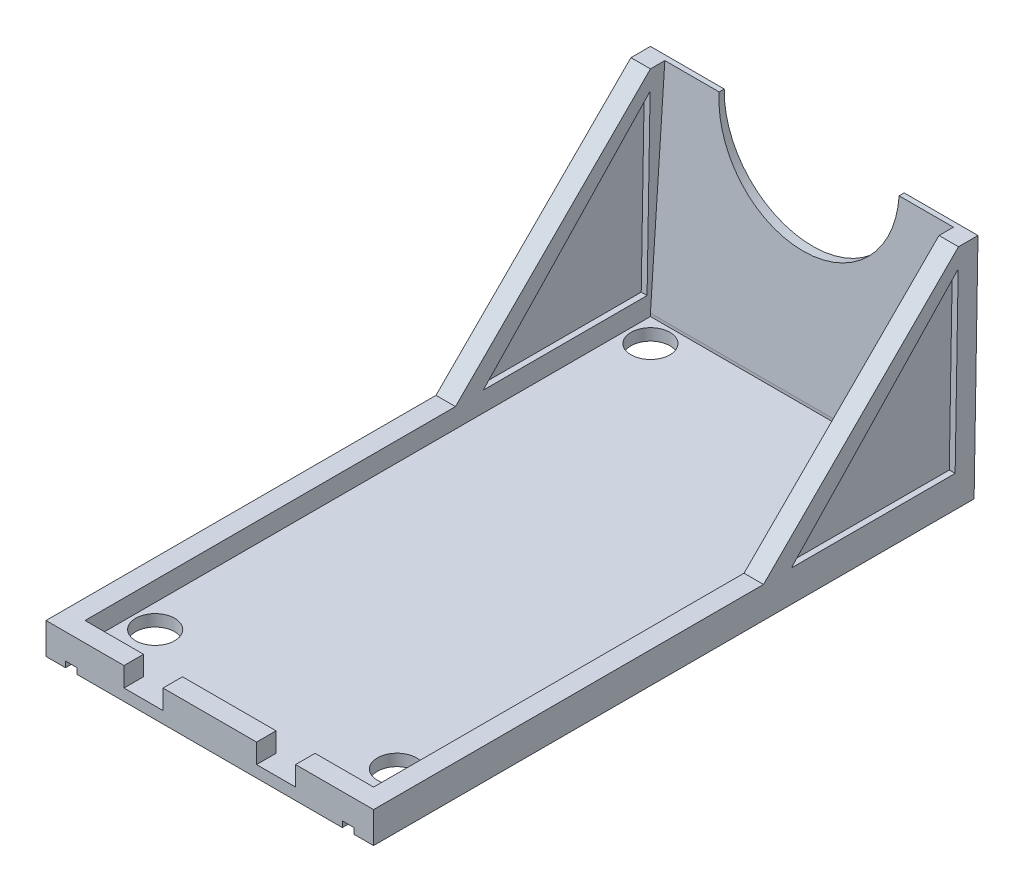
SolidWorks part; units mm, degrees
ref_plane "Front Plane" through (0, 0, 0) normal (0, 0, 1) x (1, 0, 0)
ref_plane "Top Plane" through (0, 0, 0) normal (0, 1, 0) x (1, 0, 0)
ref_plane "Right Plane" through (0, 0, 0) normal (1, 0, 0) x (0, 0, -1)
sketch "Sketch1" plane through (0, 0, 0) normal (0, 1, 0) x (1, 0, 0)
  line L1 (42, -77.5) -> (-42, -77.5)
  line L2 (42, -77.5) -> (42, 77.5)
  line L3 (42, 77.5) -> (-42, 77.5)
  line L4 (-42, -77.5) -> (-42, 77.5)
  line L5 (42, -77.5) -> (-42, 77.5) construction
  line L6 (42, 77.5) -> (-42, -77.5) construction
  point P0 (0, 0)
  dimension "D1" = 84
  dimension "D2" = 155
extrude "Boss-Extrude1" add sketch "Sketch1" along normal blind 3
sketch "Sketch2" plane through (0, 3, 0) normal (0, 1, 0) x (1, 0, 0)
  line L0 (42, -77.5) -> (42, 77.5) construction
  line L1 (37, -72.5) -> (34, -72.5)
  line L2 (37, -72.5) -> (37, -69.5)
  line L3 (37, -69.5) -> (34, -69.5)
  line L4 (34, -72.5) -> (34, -69.5)
  line L5 (-42, -77.5) -> (42, -77.5) construction
  line L6 (-42, 77.5) -> (-42, -77.5) construction
  line L7 (-37, -69.5) -> (-34, -69.5)
  line L8 (-37, -69.5) -> (-37, -72.5)
  line L9 (-37, -72.5) -> (-34, -72.5)
  line L10 (-34, -69.5) -> (-34, -72.5)
  dimension "D1" = 5
  dimension "D2" = 5
  dimension "D3" = 3
  dimension "D4" = 3
  dimension "D5" = 5
  dimension "D6" = 5
  dimension "D7" = 3
  dimension "D8" = 3
extrude "Cut-Extrude1" cut sketch "Sketch2" against normal blind 3
sketch "Sketch3" plane through (0, 0, 77.5) normal (0, 0, 1) x (1, 0, 0)
  line L0 (-42, 3) -> (42, 3) construction
  line L1 (42, 0) -> (37, 0)
  line L2 (42, 0) -> (42, 8)
  line L3 (42, 8) -> (37, 8)
  line L4 (37, 0) -> (37, 8)
  dimension "D1" = 5
  dimension "D2" = 5
extrude "Boss-Extrude2" add sketch "Sketch3" against normal blind 155
sketch "Sketch4" plane through (0, 0, 77.5) normal (0, 0, 1) x (1, 0, 0)
  line L0 (-42, 3) -> (37, 3) construction
  line L1 (-42, 0) -> (-37, 0)
  line L2 (-42, 0) -> (-42, 8)
  line L3 (-42, 8) -> (-37, 8)
  line L4 (-37, 0) -> (-37, 8)
  dimension "D1" = 5
  dimension "D2" = 5
extrude "Boss-Extrude3" add sketch "Sketch4" against normal blind 155
sketch "Sketch5" plane through (-42, 0, 0) normal (-1, 0, 0) x (0, 0, 1)
  line L0 (-77.5, 8) -> (77.5, 8) construction
  line L1 (-77.5, 0) -> (-72.5, 0)
  line L2 (-77.5, 0) -> (-77.5, 58)
  line L3 (-77.5, 58) -> (-72.5, 58)
  line L4 (-72.5, 0) -> (-72.5, 58)
  dimension "D1" = 5
  dimension "D2" = 50
extrude "Boss-Extrude4" add sketch "Sketch5" against normal blind 84
sketch "Sketch6" plane through (-42, 0, 0) normal (-1, 0, 0) x (0, 0, 1)
  line L0 (-72.5, 58) -> (-22.5, 8)
  line L1 (-72.5, 8) -> (77.5, 8) construction
  line L2 (-22.5, 8) -> (-74.3, 4.4168)
  line L3 (-74.3, 4.4168) -> (-74.3, 56.2)
  line L4 (-74.3, 56.2) -> (-72.5, 58)
extrude "Boss-Extrude5" add sketch "Sketch6" against normal blind 5
sketch "Sketch7" plane through (42, 0, 0) normal (1, 0, 0) x (0, 0, -1)
  line L0 (72.5, 58) -> (19.1089, 4.6089)
  line L1 (19.1089, 4.6089) -> (75.2476, 4.6089)
  line L2 (75.2476, 4.6089) -> (75.2476, 53.9164)
  line L3 (75.2476, 53.9164) -> (72.5, 58)
extrude "Boss-Extrude6" add sketch "Sketch7" against normal blind 5
sketch "Sketch8" plane through (0, 0, 77.5) normal (0, 0, 1) x (1, 0, 0)
  line L1 (42, 0) -> (-42, 0)
  line L2 (42, 0) -> (42, 8)
  line L3 (42, 8) -> (-42, 8)
  line L4 (-42, 0) -> (-42, 8)
extrude "Boss-Extrude8" add sketch "Sketch8" against normal blind 5
sketch "Sketch10" plane through (0, 0, 77.5) normal (0, 0, 1) x (1, 0, 0)
  line L0 (-42, 0) -> (42, 0) construction
  line L1 (-22, 3) -> (-12, 3)
  line L2 (-22, 3) -> (-22, 10.4972)
  line L3 (-22, 10.4972) -> (-12, 10.4972)
  line L4 (-12, 3) -> (-12, 10.4972)
  line L5 (-42, 8) -> (-42, 0) construction
  dimension "D1" = 3
  dimension "D2" = 20
  dimension "D3" = 10
extrude "Cut-Extrude2" cut sketch "Sketch10" against normal blind 5
sketch "Sketch11" plane through (0, 0, 77.5) normal (0, 0, 1) x (1, 0, 0)
  line L0 (42, 8) -> (42, 0) construction
  line L1 (22, 3) -> (12, 3)
  line L2 (22, 3) -> (22, 13.6666)
  line L3 (22, 13.6666) -> (12, 13.6666)
  line L4 (12, 3) -> (12, 13.6666)
  line L5 (-42, 0) -> (42, 0) construction
  dimension "D1" = 10
  dimension "D2" = 20
  dimension "D3" = 3
extrude "Cut-Extrude3" cut sketch "Sketch11" against normal blind 5
sketch "Sketch12" plane through (0, 0, 0) normal (0, -1, 0) x (-1, 0, 0)
  line L0 (42, -77.5) -> (-42, -77.5) construction
  line L1 (37, -72.5) -> (34.0087, -72.5)
  line L2 (37, -72.5) -> (37, -77.5)
  line L3 (37, -77.5) -> (34.0087, -77.5)
  line L4 (34.0087, -72.5) -> (34.0087, -77.5)
extrude "Cut-Extrude4" cut sketch "Sketch12" against normal blind 1.5
sketch "Sketch13" plane through (0, 0, 0) normal (0, -1, 0) x (-1, 0, 0)
  line L0 (-34, -72.5) -> (-34, -80.1939)
  line L1 (-37, -72.5) -> (-37, -80.0754)
  line L2 (-37, -80.0754) -> (-34, -80.1939)
  line L3 (-34, -72.5) -> (-37, -72.5)
extrude "Cut-Extrude5" cut sketch "Sketch13" against normal blind 1.5
sketch "Sketch14" plane through (0, 3, 0) normal (0, 1, 0) x (1, 0, 0)
  line L0 (-37, 22.5) -> (-37, 72.5) construction
  line L1 (-37, 72.5) -> (37, 72.5) construction
  circle A0 centre (-31, 66.5) radius 5
  dimension "D1" = 6
  dimension "D2" = 6
extrude "Cut-Extrude6" cut sketch "Sketch14" against normal blind 10
sketch "Sketch15" plane through (0, 3, 0) normal (0, 1, 0) x (1, 0, 0)
  line L0 (37, 72.5) -> (37, -69.5) construction
  line L1 (-37, 72.5) -> (37, 72.5) construction
  circle A0 centre (31, 66.5) radius 5
  dimension "D1" = 6
  dimension "D2" = 6
extrude "Cut-Extrude7" cut sketch "Sketch15" against normal blind 10
sketch "Sketch16" plane through (0, 3, 0) normal (0, 1, 0) x (1, 0, 0)
  line L0 (-37, 22.5) -> (-37, -72.5) construction
  line L1 (-22, -72.5) -> (-37, -72.5) construction
  line L2 (37, 22.5) -> (37, -72.5) construction
  line L3 (37, -72.5) -> (22, -72.5) construction
  circle A0 centre (-31, -60.5) radius 5
  circle A1 centre (31, -60.5) radius 5
  dimension "D1" = 6
  dimension "D2" = 12
  dimension "D3" = 6
  dimension "D4" = 12
extrude "Cut-Extrude8" cut sketch "Sketch16" against normal blind 10
sketch "Sketch18" plane through (-42, 0, 0) normal (-1, 0, 0) x (0, 0, 1)
  line L0 (-72.5, 58) -> (-76.1986, 58)
  line L1 (-72.5, 58) -> (-77.5, 58) construction
  line L6 (-72.5, 3.7436) -> (-76.1986, 58)
  line L7 (-72.5, 58) -> (-72.5, 3.7436)
extrude "Cut-Extrude9" cut sketch "Sketch18" against normal blind 90
sketch "Sketch19" plane through (-42, 0, 0) normal (-1, 0, 0) x (0, 0, 1)
  line L0 (-77.5, 0) -> (-76.5, 0)
  line L2 (-77.5, 0) -> (77.5, 0) construction
  line L3 (-76.5, 0) -> (-77.5, 58)
  line L4 (-77.5, 58) -> (-77.5, 0)
extrude "Cut-Extrude10" cut sketch "Sketch19" against normal blind 90
sketch "Sketch20" plane through (-42, 0, 0) normal (-1, 0, 0) x (0, 0, 1)
  line L0 (-76.1986, 58) -> (-72.5, 58)
  line L1 (-72.5, 58) -> (-70.7879, 0)
  line L2 (-76.5, 0) -> (77.5, 0) construction
  line L3 (-70.7879, 0) -> (-74.3493, 0)
  line L4 (-74.3493, 0) -> (-76.1986, 58)
extrude "Boss-Extrude9" add sketch "Sketch20" against normal blind 5
sketch "Sketch21" plane through (42, 0, 0) normal (1, 0, 0) x (0, 0, -1)
  line L0 (76.1986, 58) -> (72.5, 58)
  line L1 (72.5, 58) -> (70.7371, 0)
  line L2 (-77.5, 0) -> (76.5, 0) construction
  line L3 (70.7371, 0) -> (74.8789, 0)
  line L4 (74.8789, 0) -> (76.1986, 58)
  line L5 (76.1986, 58) -> (76.312, 58.3378)
extrude "Boss-Extrude10" add sketch "Sketch21" against normal blind 5 contours L0 L1 L3 L4
sketch "Sketch22" plane through (42, 0, 0) normal (1, 0, 0) x (0, 0, -1)
  line L0 (72.1773, 51.2852) -> (29.7634, 8.8713)
  line L1 (29.7634, 8.8713) -> (72.1773, 8.8713)
  line L2 (72.1773, 8.8713) -> (72.1773, 51.2852)
extrude "Cut-Extrude11" cut sketch "Sketch22" against normal blind 1.5
sketch "Sketch23" plane through (37, 0, 0) normal (-1, 0, 0) x (0, 0, 1)
  line L0 (-71.6725, 51.5182) -> (-71.6725, 9.2624)
  line L1 (-71.6725, 9.2624) -> (-29.2749, 9.2624)
  line L2 (-29.2749, 9.2624) -> (-71.6725, 51.5182)
extrude "Cut-Extrude12" cut sketch "Sketch23" against normal blind 1.5
sketch "Sketch24" plane through (-42, 0, 0) normal (-1, 0, 0) x (0, 0, 1)
  line L0 (-71.6725, 51.5182) -> (-71.6725, 9.2624)
  line L1 (-71.6725, 9.2624) -> (-29.2749, 9.2624)
  line L2 (-29.2749, 9.2624) -> (-71.6725, 51.5182)
extrude "Cut-Extrude13" cut sketch "Sketch24" against normal blind 1.5
sketch "Sketch25" plane through (-37, 0, 0) normal (1, 0, 0) x (0, 0, -1)
  line L0 (72.1773, 51.2852) -> (29.7634, 8.8713)
  line L1 (29.7634, 8.8713) -> (71.6725, 9.2624)
  line L2 (71.6725, 9.2624) -> (72.1773, 51.2852)
extrude "Cut-Extrude14" cut sketch "Sketch25" against normal blind 1.5
sketch "Sketch26" plane through (-42, 0, 0) normal (-1, 0, 0) x (0, 0, 1)
  line L1 (-72.9302, 7.2144) -> (-23.3794, 7.2144)
  line L2 (-72.9302, 7.2144) -> (-72.9302, 54.9407)
  line L3 (-72.9302, 54.9407) -> (-23.3794, 54.9407)
  line L4 (-23.3794, 7.2144) -> (-23.3794, 54.9407)
extrude "Boss-Extrude14" add sketch "Sketch26" against normal blind 5
sketch "Sketch28" plane through (-42, 0, 0) normal (-1, 0, 0) x (0, 0, 1)
  line L0 (-72.5, 58) -> (-22.5, 8)
  line L1 (-22.5, 8) -> (-3.82, 78.8144)
  line L2 (-3.82, 78.8144) -> (-53.5672, 70.303)
  line L3 (-53.5672, 70.303) -> (-72.5, 58)
extrude "Cut-Extrude16" cut sketch "Sketch28" against normal blind 5
sketch "Sketch29" plane through (42, 0, 0) normal (1, 0, 0) x (0, 0, -1)
  line L0 (29.7634, 8.8713) -> (72.1773, 51.2852)
  line L1 (72.1773, 51.2852) -> (75.2299, 8.8713)
  line L2 (75.2299, 8.8713) -> (31.7112, 2.8296)
  line L3 (31.7112, 2.8296) -> (29.7634, 8.8713)
extrude "Boss-Extrude15" add sketch "Sketch29" against normal blind 5
sketch "Sketch30" plane through (42, 0, 0) normal (1, 0, 0) x (0, 0, -1)
  line L3 (72.4145, 53.0869) -> (71.6388, 8.0936)
  line L4 (71.6388, 8.0936) -> (29.6388, 8.0936)
  line L5 (29.6388, 8.0936) -> (72.4145, 53.0869)
extrude "Cut-Extrude17" cut sketch "Sketch30" against normal blind 1.5
sketch "Sketch31" plane through (37, 0, 0) normal (-1, 0, 0) x (0, 0, 1)
  line L0 (-72.1022, 54.6289) -> (-24.3271, 8.2708)
  line L1 (-24.3271, 8.2708) -> (-37.7546, 5.8824)
  line L2 (-37.7546, 5.8824) -> (-74.8781, 49.6732)
  line L3 (-74.8781, 49.6732) -> (-72.1022, 54.6289)
extrude "Boss-Extrude16" add sketch "Sketch31" against normal blind 1.5
sketch "Sketch32" plane through (37, 0, 0) normal (-1, 0, 0) x (0, 0, 1)
  line L0 (-72.4145, 53.0869) -> (-71.6388, 8.0936)
  line L1 (-71.6388, 8.0936) -> (-29.6388, 8.0936)
  line L2 (-29.6388, 8.0936) -> (-72.4145, 53.0869)
extrude "Cut-Extrude18" cut sketch "Sketch32" against normal blind 1.5
sketch "Sketch33" plane through (-42, 0, 0) normal (-1, 0, 0) x (0, 0, 1)
  line L0 (-72.4145, 53.0869) -> (-71.6388, 8.0936)
  line L1 (-71.6388, 8.0936) -> (-29.6388, 8.0936)
  line L2 (-29.6388, 8.0936) -> (-72.4145, 53.0869)
  line L3 (-72.4145, 53.0869) -> (-72.126, 52.8747)
extrude "Cut-Extrude19" cut sketch "Sketch33" against normal blind 1.5 contours L1 L2 L0 region at (-42, 23.0914, -57.8974)
sketch "Sketch34" plane through (-37, 0, 0) normal (1, 0, 0) x (0, 0, -1)
  line L0 (72.4145, 53.0869) -> (71.6388, 8.0936)
  line L1 (71.6388, 8.0936) -> (29.6388, 8.0936)
  line L2 (29.6388, 8.0936) -> (72.4145, 53.0869)
extrude "Cut-Extrude20" cut sketch "Sketch34" against normal blind 1.5
sketch "Sketch35" plane through (0, -4.9021, -71.9106) normal (0, 0.068, 0.9977) x (1, 0, 0)
  line L0 (37, 63.0481) -> (-37, 63.0481) construction
  circle A0 centre (0, 63.0481) radius 23.0767
extrude "Cut-Extrude21" cut sketch "Sketch35" against normal blind 10
